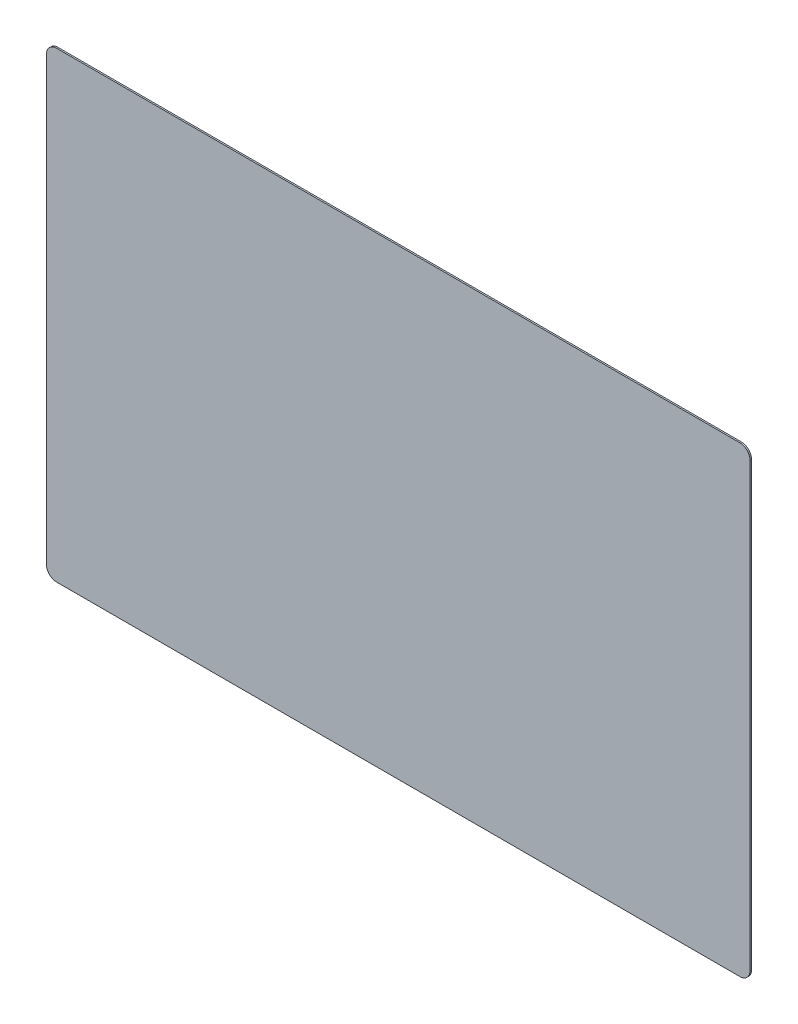
SolidWorks part; units mm, degrees
material "1.0037 (S235JR)"
ref_plane "Front Plane" through (0, 0, 0) normal (0, 0, 1) x (1, 0, 0)
ref_plane "Top Plane" through (0, 0, 0) normal (0, 1, 0) x (1, 0, 0)
ref_plane "Right Plane" through (0, 0, 0) normal (1, 0, 0) x (0, 0, -1)
sketch "Sketch1" plane through (0, 0, 0) normal (0, 0, 1) x (1, 0, 0)
  line L1 (350, -230) -> (-350, -230)
  line L2 (350, -230) -> (350, 230)
  line L3 (350, 230) -> (-350, 230)
  line L4 (-350, -230) -> (-350, 230)
  line L5 (350, -230) -> (-350, 230) construction
  line L6 (350, 230) -> (-350, -230) construction
  point P0 (0, 0)
  dimension "D1" = 700
  dimension "D2" = 460
base flange "Base-Flange1" sketch "Sketch1" thickness 1.5 reverse thickness direction no parameters "D1"=0.7366
fillet "Fillet1" radius 10 4 edges at (350, -230, -0.75) (350, 230, -0.75) (-350, 230, -0.75) (-350, -230, -0.75)
sketch "Bend-Lines1" [suppressed] plane through (0, 0, 0) normal (0, 1, 0) x (1, 0, 0)
sketch "Bounding-Box1" [suppressed] plane through (0, 0, 0) normal (0, 1, 0) x (1, 0, 0)
sheet metal parameters "Sheet-Metal1" thickness 1.5 parameters "D1"=0.7366
flat pattern "Flat-Pattern1" [suppressed]
sketch "Bend-Lines2" plane through (0, 0, 0) normal (0, 1, 0) x (1, 0, 0)
sketch3d "Bounding-Box2" [suppressed]
  line L0 (-350, 230, 0) -> (350, 230, 0) construction
  line L1 (-350, -230, 0) -> (350, -230, 0) construction
  line L2 (-350, 230, 0) -> (-350, -230, 0) construction
  line L3 (350, 230, 0) -> (350, -230, 0) construction
